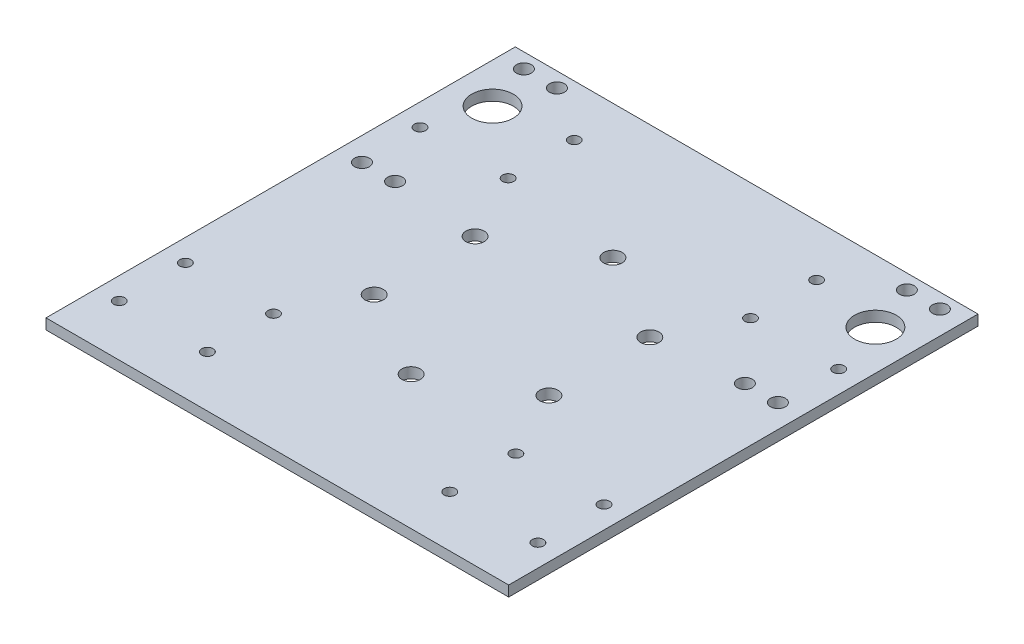
SolidWorks part; units mm, degrees
ref_plane "Front Plane" through (0, 0, 0) normal (0, 0, 1) x (1, 0, 0)
ref_plane "Top Plane" through (0, 0, 0) normal (0, 1, 0) x (1, 0, 0)
ref_plane "Right Plane" through (0, 0, 0) normal (1, 0, 0) x (0, 0, -1)
sketch "Sketch1" plane through (0, 0, 0) normal (0, 1, 0) x (1, 0, 0)
  line L1 (-70, -71) -> (70, -71)
  line L2 (-70, -71) -> (-70, 71)
  line L3 (-70, 71) -> (70, 71)
  line L4 (70, -71) -> (70, 71)
  line L5 (-70, -71) -> (70, 71) construction
  line L6 (-70, 71) -> (70, -71) construction
  point P0 (0, 0)
  dimension "D1" = 140
  dimension "D2" = 142
extrude "Boss-Extrude1" add sketch "Sketch1" along normal blind 3.175
sketch "Sketch2" plane through (0, 3.175, 0) normal (0, 1, 0) x (1, 0, 0)
  line L0 (-45, 30.5) -> (-30, 30.5) construction
  line L1 (-45, -30.5) -> (45, -30.5) construction
  line L2 (-45, -30.5) -> (-45, 30.5) construction
  line L3 (-45, 30.5) -> (45, 30.5) construction
  line L4 (45, -30.5) -> (45, 30.5) construction
  line L5 (-45, -30.5) -> (45, 30.5) construction
  line L6 (-45, 30.5) -> (45, -30.5) construction
  line L7 (-30, 30.5) -> (-30, 60.5) construction
  line L8 (-70, 71) -> (-70, -71) construction
  line L9 (-30, 60.5) -> (-70, 60.5) construction
  line L10 (-30, 60.5) -> (-30, 30.5) construction
  line L11 (-30, 30.5) -> (-70, 30.5) construction
  line L12 (-70, 60.5) -> (-70, 30.5) construction
  line L13 (-30, 60.5) -> (-70, 30.5) construction
  line L14 (-30, 30.5) -> (-70, 60.5) construction
  line L15 (-51.4643, -23.9643) -> (-51.4643, 60.5) construction
  line L16 (-70, 45.5) -> (-30, 45.5) construction
  line L17 (-50, 60.5) -> (-50, 30.5) construction
  line L18 (-57.9286, 52.0357) -> (-57.9286, 62.0357) construction
  line L19 (-62.9286, 66.5357) -> (-52.9286, 66.5357) construction
  line L20 (-67.9286, 62.0357) -> (-47.9286, 62.0357) construction
  line L21 (-67.9286, 62.0357) -> (-67.9286, 22.0357) construction
  line L22 (-67.9286, 22.0357) -> (-47.9286, 22.0357) construction
  line L23 (-47.9286, 62.0357) -> (-47.9286, 22.0357) construction
  line L24 (-67.9286, 62.0357) -> (-47.9286, 22.0357) construction
  line L25 (-67.9286, 22.0357) -> (-47.9286, 62.0357) construction
  line L26 (-67.9286, 17.5357) -> (-47.9286, 17.5357) construction
  line L27 (-67.9286, 17.5357) -> (-67.9286, 66.5357) construction
  line L28 (-67.9286, 66.5357) -> (-47.9286, 66.5357) construction
  line L29 (-47.9286, 17.5357) -> (-47.9286, 66.5357) construction
  line L30 (-67.9286, 17.5357) -> (-47.9286, 66.5357) construction
  line L31 (-67.9286, 66.5357) -> (-47.9286, 17.5357) construction
  line L32 (-67.9286, 14.0357) -> (-47.9286, 14.0357) construction
  line L33 (-67.9286, 14.0357) -> (-67.9286, 70.0357) construction
  line L34 (-67.9286, 70.0357) -> (-47.9286, 70.0357) construction
  line L35 (-47.9286, 14.0357) -> (-47.9286, 70.0357) construction
  line L36 (-67.9286, 14.0357) -> (-47.9286, 70.0357) construction
  line L37 (-67.9286, 70.0357) -> (-47.9286, 14.0357) construction
  line L38 (-67.9286, 42.0357) -> (-47.9286, 42.0357) construction
  line L39 (0, -1.7463) -> (0, 1.7463) construction
  line L40 (-45, 30.5) -> (-45, 45.5) construction
  line L41 (-1.7463, 0) -> (1.7463, 0) construction
  line L42 (-67.9286, 52.0357) -> (-30, 52.0357) construction
  circle A0 centre (-45, 0) radius 6.4643 construction
  circle A1 centre (-57.9286, 52.0357) radius 6.4643 construction
  circle A2 centre (-57.9286, 52.0357) radius 6.3
  circle A8 centre (-57.9286, 52.0357) radius 2.45 construction
  circle A9 centre (-62.9286, 66.5357) radius 2.25
  circle A10 centre (-52.9286, 66.5357) radius 2.25
  circle A11 centre (-52.9286, 17.5357) radius 2.25
  circle A12 centre (-62.9286, 17.5357) radius 2.25
  circle A13 centre (52.9286, 17.5357) radius 2.25
  circle A14 centre (62.9286, 17.5357) radius 2.25
  circle A15 centre (57.9286, 52.0357) radius 6.3
  circle A16 centre (52.9286, 66.5357) radius 2.25
  circle A17 centre (62.9286, 66.5357) radius 2.25
  circle A18 centre (-36.6667, 55.5) radius 1.7
  circle A19 centre (-36.6667, 35.5) radius 1.7
  circle A20 centre (-63.3333, 35.5) radius 1.7
  circle A21 centre (-63.3333, 55.5) radius 1.7 construction
  circle A22 centre (36.6667, 35.5) radius 1.7
  circle A23 centre (63.3333, 35.5) radius 1.7
  circle A24 centre (36.6667, 55.5) radius 1.7
  circle A25 centre (63.3333, 55.5) radius 1.7 construction
  circle A26 centre (63.3333, -35.5) radius 1.7
  circle A27 centre (36.6667, -35.5) radius 1.7
  circle A28 centre (63.3333, -55.5) radius 1.7
  circle A29 centre (36.6667, -55.5) radius 1.7
  circle A30 centre (-36.6667, -35.5) radius 1.7
  circle A31 centre (-63.3333, -35.5) radius 1.7
  circle A32 centre (-36.6667, -55.5) radius 1.7
  circle A33 centre (-63.3333, -55.5) radius 1.7
  point P0 (0, 0)
  point P10 (-50, 45.5)
  point P25 (-57.9286, 42.0357)
  point P31 (-57.9286, 42.0357)
  point P32 (-57.9286, 62.0357)
  point P37 (-57.9286, 42.0357)
  point P44 (-57.9286, 66.5357)
  point P45 (-57.9286, 66.5357)
  dimension "D5" = 12.9286
  dimension "D6" = 12.9286
  dimension "D7" = 12.6
  dimension "D8" = 4.9
  dimension "D14" = 10
  dimension "D9" = 10
  dimension "4.5" = 4.5
  dimension "D16" = 3.4
  dimension "D1" = 90
  dimension "D2" = 61
  dimension "D3" = 15
  dimension "D4" = 30
  dimension "D10" = 20
  dimension "D11" = 40
  dimension "D12" = 49
  dimension "D13" = 56
  dimension "D17" = 5
  dimension "D18" = 8.4643
sketch "Sketch4" plane through (0, 3.175, 0) normal (0, 1, 0) x (1, 0, 0)
  line L0 (0, 0) -> (0, 30.525) construction
  line L1 (0, 0) -> (26.4354, 15.2625) construction
  circle A0 centre (0, 0) radius 40 construction
  circle A1 centre (0, 0) radius 30.525 construction
  circle A2 centre (0, 30.525) radius 2.7781
  circle A3 centre (26.4354, 15.2625) radius 2.7781
  circle A4 centre (26.4354, -15.2625) radius 2.7781
  circle A5 centre (0, -30.525) radius 2.7781
  circle A6 centre (-26.4354, -15.2625) radius 2.7781
  circle A7 centre (-26.4354, 15.2625) radius 2.7781
  dimension "D1" = 80
  dimension "D2" = 61.05
  dimension "D3" = 5.5563
  dimension "D5" = 60
  dimension "D4" = 6
extrude "Cut-Extrude1" cut sketch "Sketch2" against normal up to surface (3.175 mm away) contours A9 | A10 | A18 | A2 | A19 | A20 | A11 | A12 | A16 | A17 | A24 | A15 | A23 | A22 | A13 | A14 | A31 | A30 | A33 | A32 | A27 | A26 | A29 | A28 up to face at (0, 0, 0)
extrude "Cut-Extrude2" cut sketch "Sketch4" against normal up to surface (3.175 mm away) contours A7 | A2 | A3 | A6 | A4 | A5 up to face at (57.9286, 0, -58.3357)
